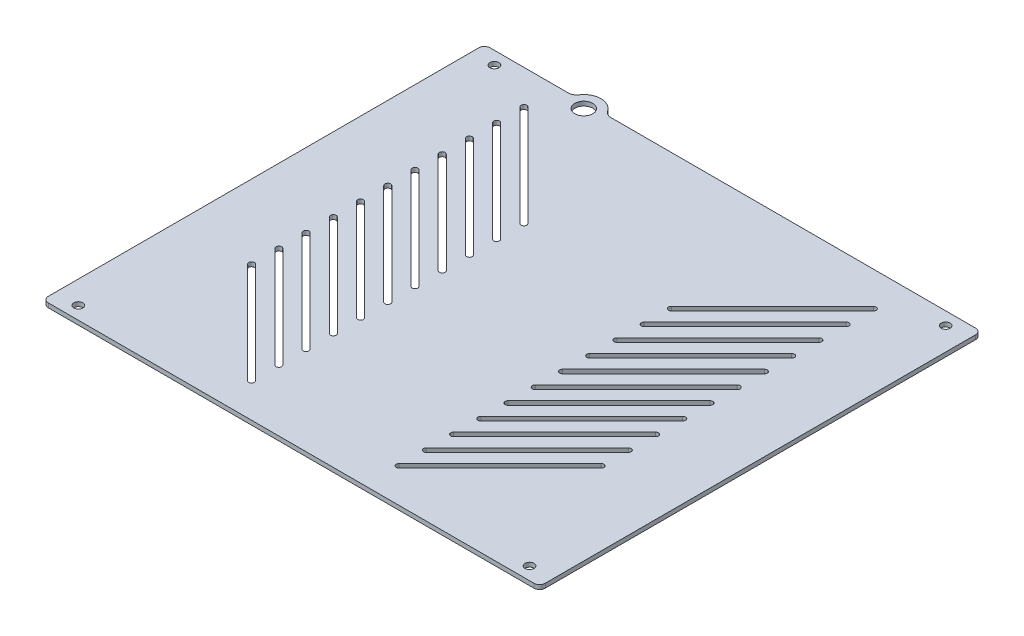
SolidWorks part; units mm, degrees
material "1.0037 (S235JR)"
ref_plane "Front Plane" through (0, 0, 0) normal (0, 0, 1) x (1, 0, 0)
ref_plane "Top Plane" through (0, 0, 0) normal (0, 1, 0) x (1, 0, 0)
ref_plane "Right Plane" through (0, 0, 0) normal (1, 0, 0) x (0, 0, -1)
sketch "Sketch1" plane through (0, 0, 0) normal (0, 1, 0) x (1, 0, 0)
  line L1 (87, -77.35) -> (-87, -77.35)
  line L2 (87, -77.35) -> (87, 77.35)
  line L3 (87, 77.35) -> (-87, 77.35)
  line L4 (-87, -77.35) -> (-87, 77.35)
  line L5 (87, -77.35) -> (-87, 77.35) construction
  line L6 (87, 77.35) -> (-87, -77.35) construction
  line L7 (79, -72.85) -> (-79, -72.85) construction
  line L8 (79, -72.85) -> (79, 72.85) construction
  line L9 (79, 72.85) -> (-79, 72.85) construction
  line L10 (-79, -72.85) -> (-79, 72.85) construction
  line L11 (79, -72.85) -> (-79, 72.85) construction
  line L12 (79, 72.85) -> (-79, -72.85) construction
  circle A0 centre (-79, 72.85) radius 1.575
  circle A1 centre (79, 72.85) radius 1.575
  circle A2 centre (79, -72.85) radius 1.575
  circle A3 centre (-79, -72.85) radius 1.575
  point P0 (0, 0)
  point P5 (0, 0)
  dimension "D5" = 3.15
  dimension "D1" = 154.7
  dimension "D2" = 174
  dimension "D3" = 145.7
  dimension "D4" = 158
base flange "Base-Flange1" sketch "Sketch1" thickness 1.5 reverse thickness direction no parameters "D1"=1.65
fillet "Fillet1" radius 2 4 edges at (-87, -0.75, -77.35) (87, -0.75, -77.35) (-87, -0.75, 77.35) (87, -0.75, 77.35)
sketch "Sketch6" plane through (0, 0, 0) normal (0, 1, 0) x (1, 0, 0)
  line L0 (0, -77.35) -> (0, 77.35) construction
  line L1 (-85, -77.35) -> (85, -77.35) construction
  line L2 (85, 77.35) -> (-85, 77.35) construction
  line L3 (25.8223, -65.35) -> (61.1777, -29.9947) construction
  line L4 (0, -77.35) -> (87, -77.35) construction
  line L5 (87, -77.35) -> (87, 0) construction
  line L6 (87, -75.35) -> (87, 75.35) construction
  line L7 (26.5294, -66.0571) -> (61.8848, -30.7018)
  line L8 (25.1152, -64.6429) -> (60.4706, -29.2876)
  line L9 (26.5294, -56.5226) -> (61.8848, -21.1673)
  line L10 (25.1152, -55.1084) -> (60.4706, -19.7531)
  line L11 (25.8223, -55.8155) -> (61.1777, -20.4602) construction
  line L12 (26.5294, -46.9882) -> (61.8848, -11.6328)
  line L13 (25.1152, -45.574) -> (60.4706, -10.2186)
  line L14 (25.8223, -46.2811) -> (61.1777, -10.9257) construction
  line L15 (26.5294, -37.4537) -> (61.8848, -2.0984)
  line L16 (25.1152, -36.0395) -> (60.4706, -0.6842)
  line L17 (25.8223, -36.7466) -> (61.1777, -1.3913) construction
  line L18 (26.5294, -27.9192) -> (61.8848, 7.4361)
  line L19 (25.1152, -26.505) -> (60.4706, 8.8503)
  line L20 (25.8223, -27.2121) -> (61.1777, 8.1432) construction
  line L21 (26.5294, -18.3848) -> (61.8848, 16.9706)
  line L22 (25.1152, -16.9706) -> (60.4706, 18.3848)
  line L23 (25.8223, -17.6777) -> (61.1777, 17.6777) construction
  line L24 (26.5294, -8.8503) -> (61.8848, 26.505)
  line L25 (25.1152, -7.4361) -> (60.4706, 27.9192)
  line L26 (25.8223, -8.1432) -> (61.1777, 27.2121) construction
  line L27 (26.5294, 0.6842) -> (61.8848, 36.0395)
  line L28 (25.1152, 2.0984) -> (60.4706, 37.4537)
  line L29 (25.8223, 1.3913) -> (61.1777, 36.7466) construction
  line L30 (26.5294, 10.2186) -> (61.8848, 45.574)
  line L31 (25.1152, 11.6328) -> (60.4706, 46.9882)
  line L32 (25.8223, 10.9257) -> (61.1777, 46.2811) construction
  line L33 (26.5294, 19.7531) -> (61.8848, 55.1084)
  line L34 (25.1152, 21.1673) -> (60.4706, 56.5226)
  line L35 (25.8223, 20.4602) -> (61.1777, 55.8155) construction
  line L36 (26.5294, 29.2876) -> (61.8848, 64.6429)
  line L37 (25.1152, 30.7018) -> (60.4706, 66.0571)
  line L38 (25.8223, 29.9947) -> (61.1777, 65.35) construction
  line L39 (-25.8223, 29.9947) -> (-61.1777, 65.35) construction
  line L40 (-25.8223, 20.4602) -> (-61.1777, 55.8155) construction
  line L41 (-25.8223, 10.9257) -> (-61.1777, 46.2811) construction
  line L42 (-25.8223, 1.3913) -> (-61.1777, 36.7466) construction
  line L43 (-25.8223, -8.1432) -> (-61.1777, 27.2121) construction
  line L44 (-25.8223, -17.6777) -> (-61.1777, 17.6777) construction
  line L45 (-25.8223, -27.2121) -> (-61.1777, 8.1432) construction
  line L46 (-25.8223, -36.7466) -> (-61.1777, -1.3913) construction
  line L47 (-25.8223, -46.2811) -> (-61.1777, -10.9257) construction
  line L48 (-25.8223, -55.8155) -> (-61.1777, -20.4602) construction
  line L49 (-87, -77.35) -> (-87, 0) construction
  line L50 (-25.8223, -65.35) -> (-61.1777, -29.9947) construction
  line L51 (-25.1152, 30.7018) -> (-60.4706, 66.0571)
  line L52 (-26.5294, 29.2876) -> (-61.8848, 64.6429)
  line L53 (-25.1152, 21.1673) -> (-60.4706, 56.5226)
  line L54 (-26.5294, 19.7531) -> (-61.8848, 55.1084)
  line L55 (-25.1152, 11.6328) -> (-60.4706, 46.9882)
  line L56 (-26.5294, 10.2186) -> (-61.8848, 45.574)
  line L57 (-25.1152, 2.0984) -> (-60.4706, 37.4537)
  line L58 (-26.5294, 0.6842) -> (-61.8848, 36.0395)
  line L59 (-25.1152, -7.4361) -> (-60.4706, 27.9192)
  line L60 (-26.5294, -8.8503) -> (-61.8848, 26.505)
  line L61 (-25.1152, -16.9706) -> (-60.4706, 18.3848)
  line L62 (-26.5294, -18.3848) -> (-61.8848, 16.9706)
  line L63 (-25.1152, -26.505) -> (-60.4706, 8.8503)
  line L64 (-26.5294, -27.9192) -> (-61.8848, 7.4361)
  line L65 (-25.1152, -36.0395) -> (-60.4706, -0.6842)
  line L66 (-26.5294, -37.4537) -> (-61.8848, -2.0984)
  line L67 (-25.1152, -45.574) -> (-60.4706, -10.2186)
  line L68 (-26.5294, -46.9882) -> (-61.8848, -11.6328)
  line L69 (-25.1152, -55.1084) -> (-60.4706, -19.7531)
  line L70 (-26.5294, -56.5226) -> (-61.8848, -21.1673)
  line L71 (-25.1152, -64.6429) -> (-60.4706, -29.2876)
  line L72 (-26.5294, -66.0571) -> (-61.8848, -30.7018)
  arc A0 (26.5294, -66.0571) -> (25.1152, -64.6429) centre (25.8223, -65.35) cw
  arc A1 (61.8848, -30.7018) -> (60.4706, -29.2876) centre (61.1777, -29.9947) ccw
  arc A2 (26.5294, -56.5226) -> (25.1152, -55.1084) centre (25.8223, -55.8155) cw
  arc A3 (61.8848, -21.1673) -> (60.4706, -19.7531) centre (61.1777, -20.4602) ccw
  arc A4 (26.5294, -46.9882) -> (25.1152, -45.574) centre (25.8223, -46.2811) cw
  arc A5 (61.8848, -11.6328) -> (60.4706, -10.2186) centre (61.1777, -10.9257) ccw
  arc A6 (26.5294, -37.4537) -> (25.1152, -36.0395) centre (25.8223, -36.7466) cw
  arc A7 (61.8848, -2.0984) -> (60.4706, -0.6842) centre (61.1777, -1.3913) ccw
  arc A8 (26.5294, -27.9192) -> (25.1152, -26.505) centre (25.8223, -27.2121) cw
  arc A9 (61.8848, 7.4361) -> (60.4706, 8.8503) centre (61.1777, 8.1432) ccw
  arc A10 (26.5294, -18.3848) -> (25.1152, -16.9706) centre (25.8223, -17.6777) cw
  arc A11 (61.8848, 16.9706) -> (60.4706, 18.3848) centre (61.1777, 17.6777) ccw
  arc A12 (26.5294, -8.8503) -> (25.1152, -7.4361) centre (25.8223, -8.1432) cw
  arc A13 (61.8848, 26.505) -> (60.4706, 27.9192) centre (61.1777, 27.2121) ccw
  arc A14 (26.5294, 0.6842) -> (25.1152, 2.0984) centre (25.8223, 1.3913) cw
  arc A15 (61.8848, 36.0395) -> (60.4706, 37.4537) centre (61.1777, 36.7466) ccw
  arc A16 (26.5294, 10.2186) -> (25.1152, 11.6328) centre (25.8223, 10.9257) cw
  arc A17 (61.8848, 45.574) -> (60.4706, 46.9882) centre (61.1777, 46.2811) ccw
  arc A18 (26.5294, 19.7531) -> (25.1152, 21.1673) centre (25.8223, 20.4602) cw
  arc A19 (61.8848, 55.1084) -> (60.4706, 56.5226) centre (61.1777, 55.8155) ccw
  arc A20 (26.5294, 29.2876) -> (25.1152, 30.7018) centre (25.8223, 29.9947) cw
  arc A21 (61.8848, 64.6429) -> (60.4706, 66.0571) centre (61.1777, 65.35) ccw
  arc A22 (-61.8848, 64.6429) -> (-60.4706, 66.0571) centre (-61.1777, 65.35) cw
  arc A23 (-26.5294, 29.2876) -> (-25.1152, 30.7018) centre (-25.8223, 29.9947) ccw
  arc A24 (-61.8848, 55.1084) -> (-60.4706, 56.5226) centre (-61.1777, 55.8155) cw
  arc A25 (-26.5294, 19.7531) -> (-25.1152, 21.1673) centre (-25.8223, 20.4602) ccw
  arc A26 (-61.8848, 45.574) -> (-60.4706, 46.9882) centre (-61.1777, 46.2811) cw
  arc A27 (-26.5294, 10.2186) -> (-25.1152, 11.6328) centre (-25.8223, 10.9257) ccw
  arc A28 (-61.8848, 36.0395) -> (-60.4706, 37.4537) centre (-61.1777, 36.7466) cw
  arc A29 (-26.5294, 0.6842) -> (-25.1152, 2.0984) centre (-25.8223, 1.3913) ccw
  arc A30 (-61.8848, 26.505) -> (-60.4706, 27.9192) centre (-61.1777, 27.2121) cw
  arc A31 (-26.5294, -8.8503) -> (-25.1152, -7.4361) centre (-25.8223, -8.1432) ccw
  arc A32 (-61.8848, 16.9706) -> (-60.4706, 18.3848) centre (-61.1777, 17.6777) cw
  arc A33 (-26.5294, -18.3848) -> (-25.1152, -16.9706) centre (-25.8223, -17.6777) ccw
  arc A34 (-61.8848, 7.4361) -> (-60.4706, 8.8503) centre (-61.1777, 8.1432) cw
  arc A35 (-26.5294, -27.9192) -> (-25.1152, -26.505) centre (-25.8223, -27.2121) ccw
  arc A36 (-61.8848, -2.0984) -> (-60.4706, -0.6842) centre (-61.1777, -1.3913) cw
  arc A37 (-26.5294, -37.4537) -> (-25.1152, -36.0395) centre (-25.8223, -36.7466) ccw
  arc A38 (-61.8848, -11.6328) -> (-60.4706, -10.2186) centre (-61.1777, -10.9257) cw
  arc A39 (-26.5294, -46.9882) -> (-25.1152, -45.574) centre (-25.8223, -46.2811) ccw
  arc A40 (-61.8848, -21.1673) -> (-60.4706, -19.7531) centre (-61.1777, -20.4602) cw
  arc A41 (-26.5294, -56.5226) -> (-25.1152, -55.1084) centre (-25.8223, -55.8155) ccw
  arc A42 (-61.8848, -30.7018) -> (-60.4706, -29.2876) centre (-61.1777, -29.9947) cw
  arc A43 (-26.5294, -66.0571) -> (-25.1152, -64.6429) centre (-25.8223, -65.35) ccw
  point P12 (43.5, -77.35)
  point P13 (43.5, -47.6723)
  dimension "D1" = 45
  dimension "D2" = 50
  dimension "D3" = 12
  dimension "D7" = 12
  dimension "D4" = 1
  dimension "D5" = 1
  dimension "D6" = 11
extrude "Cut-Extrude1" cut sketch "Sketch6" against normal through all normal cut yes
sketch "Sketch7" plane through (0, 0, 0) normal (0, 1, 0) x (1, 0, 0)
  circle A0 centre (-50.195, 75.35) radius 6 construction
  circle A1 centre (-50.195, 75.35) radius 6
base flange "Tab1" sketch "Sketch7" thickness 1.5 reverse thickness direction no parameters "D1"=1.65
sketch "Sketch10" plane through (0, 0, 0) normal (0, 1, 0) x (1, 0, 0)
  circle A0 centre (-50.195, 75.35) radius 3 construction
  circle A1 centre (-50.195, 75.35) radius 3 construction
  circle A2 centre (-50.195, 75.35) radius 3.15
  dimension "D1" = 6.3
extrude "Cut-Extrude2" cut sketch "Sketch10" against normal through all normal cut yes
fillet "Fillet2" radius 3 2 edges at (-55.8519, -0.75, -77.35) (-44.5381, -0.75, -77.35)
sketch "Bend-Lines1" [suppressed] plane through (0, 0, 0) normal (0, 1, 0) x (1, 0, 0)
sketch "Bounding-Box1" [suppressed] plane through (0, 0, 0) normal (0, 1, 0) x (1, 0, 0)
sheet metal parameters "Sheet-Metal1" thickness 1.5 parameters "D1"=1.65
flat pattern "Flat-Pattern1" [suppressed]
sketch "Bend-Lines2" plane through (0, 0, 0) normal (0, 1, 0) x (1, 0, 0)
sketch3d "Bounding-Box2" [suppressed]
  line L0 (-77.5, -67.7499, 0) -> (77.5, -67.75, 0) construction
  line L1 (-77.4999, 67.75, 0) -> (77.5001, 67.7499, 0) construction
  line L2 (-77.5, -67.7499, 0) -> (-77.4999, 67.75, 0) construction
  line L3 (77.5, -67.75, 0) -> (77.5001, 67.7499, 0) construction
sheet metal parameters "Sheet-Metal2" thickness 1.5 parameters "D1"=1.65
flat pattern "Flat-Pattern1"
sketch "Bend-Lines2" plane through (0, 0, 0) normal (0, 1, 0) x (1, 0, 0)
sketch3d "Bounding-Box2" [suppressed]
  line L0 (-87, -77.3499, 0) -> (87, -77.35, 0) construction
  line L1 (-86.9999, 77.35, 0) -> (87.0001, 77.3499, 0) construction
  line L2 (-87, -77.3499, 0) -> (-86.9999, 77.35, 0) construction
  line L3 (87, -77.35, 0) -> (87.0001, 77.3499, 0) construction
sheet metal parameters "Sheet-Metal3" thickness 1.5 parameters "D1"=1.65
flat pattern "Flat-Pattern3"
sketch "Bend-Lines3" plane through (0, 0, 0) normal (0, 1, 0) x (1, 0, 0)
sketch3d "Bounding-Box3" [suppressed]
  line L0 (-87, -77.35, 0) -> (87, -77.35, 0) construction
  line L1 (-87, 81.35, 0) -> (87, 81.35, 0) construction
  line L2 (-87, -77.35, 0) -> (-87, 81.35, 0) construction
  line L3 (87, -77.35, 0) -> (87, 81.35, 0) construction
sheet metal parameters "Sheet-Metal4" thickness 1.5 parameters "D1"=1.65
flat pattern "Flat-Pattern3"
sketch "Bend-Lines3" plane through (0, 0, 0) normal (0, 1, 0) x (1, 0, 0)
sketch3d "Bounding-Box3" [suppressed]
  line L0 (-87, -77.35, 0) -> (87, -77.35, 0) construction
  line L1 (-87, 81.35, 0) -> (87, 81.35, 0) construction
  line L2 (-87, -77.35, 0) -> (-87, 81.35, 0) construction
  line L3 (87, -77.35, 0) -> (87, 81.35, 0) construction
